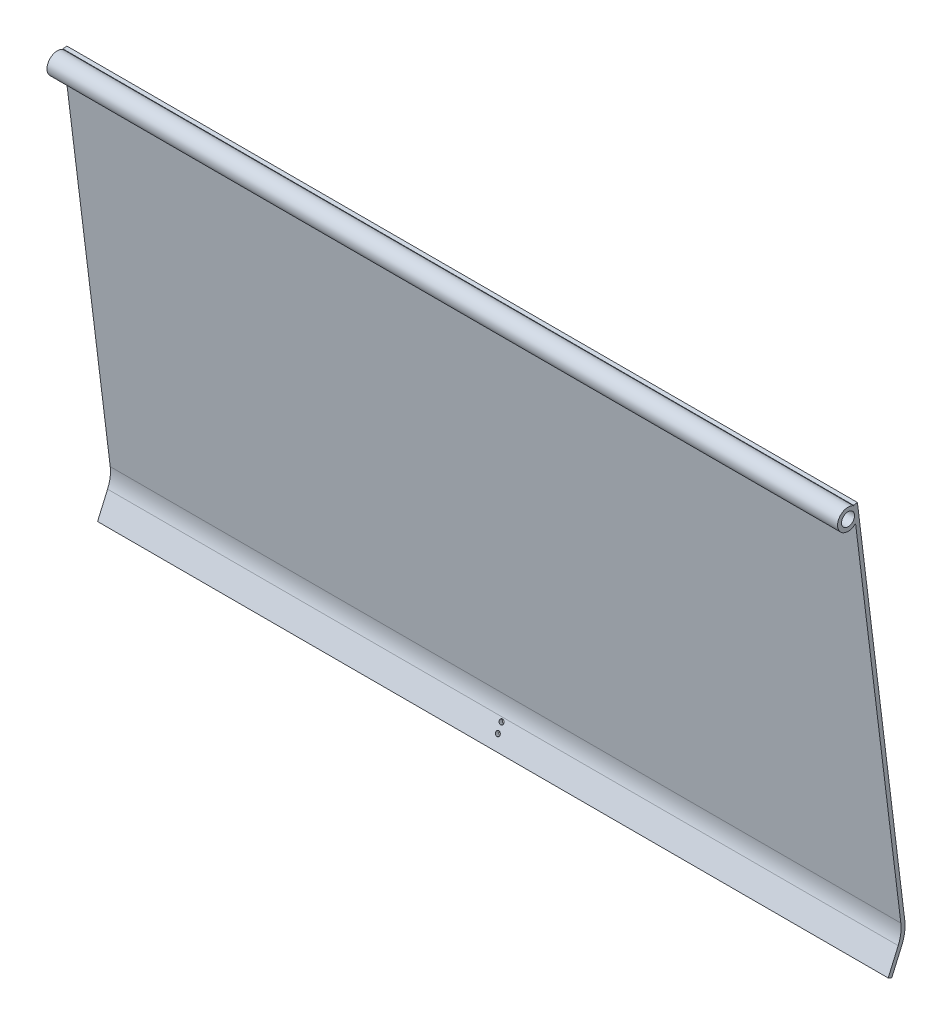
SolidWorks part; units mm, degrees
material "acero"
ref_plane "Alzado" through (0, 0, 0) normal (0, 0, 1) x (1, 0, 0)
ref_plane "Planta" through (0, 0, 0) normal (0, 1, 0) x (1, 0, 0)
ref_plane "Vista lateral" through (0, 0, 0) normal (1, 0, 0) x (0, 0, -1)
sketch "Sketch2" plane through (0, 0, 0) normal (1, 0, 0) x (0, 0, -1)
  line L2 (-441.1427, 5.3017) -> (-407.5476, 82.4956) construction
  line L3 (-405.2791, 98.1232) -> (-441.1997, 390.6725) construction
  line L4 (-441.485, 5.7681) -> (-408.0061, 82.6952)
  line L5 (-405.7754, 98.0623) -> (-441.6959, 390.6116)
  line L7 (-413.8036, 68.1207) -> (-411.0529, 66.9236) construction
  line L8 (-448.8036, 68.1207) -> (-448.8036, 383.1207) construction
  line L9 (-448.8036, 68.1207) -> (-413.8036, 68.1207) construction
  line L10 (-444.2358, 6.9653) -> (-410.7569, 83.8923)
  line L11 (-408.753, 97.6967) -> (-444.6736, 390.246)
  line L12 (-418.3654, 66.4097) -> (-415.6146, 65.2125)
  line L13 (-441.6959, 390.6116) -> (-444.6736, 390.246)
  line L14 (-405.2791, 98.1232) -> (-441.1997, 390.6725) construction
  line L15 (-441.1997, 390.6725) -> (-438.222, 391.0381) construction
  line L16 (-441.1997, 390.6725) -> (-405.2791, 98.1232) construction
  line L17 (-441.0265, 5.5686) -> (-407.5476, 82.4956) construction
  arc A1 (-407.5476, 82.4956) -> (-405.2791, 98.1232) centre (-435.0555, 94.4671) ccw construction
  arc A2 (-408.0061, 82.6952) -> (-405.7754, 98.0623) centre (-435.0555, 94.4671) ccw
  arc A3 (-410.7569, 83.8923) -> (-408.753, 97.6967) centre (-435.0555, 94.4671) ccw
  circle A4 centre (-448.8036, 383.1207) radius 4.9676
  circle A5 centre (-448.8036, 383.1207) radius 7.9676
  dimension "D2" = 315
  dimension "D3" = 35
  dimension "D4" = 3
  dimension "D1" = 0.5
extrude "Main" add sketch "Sketch2" along normal mid plane 600 contours A5 L5 L13 L11 | A5 L11 A3 L10 L12 L4 A2 L5 | A5 L11 | L11 A5 A4 region at (0, 221.9373, 423.0804) region at (0, 388.9276, 442.4547) region at (0, 383.875, 442.6604) region at (0, 386.7921, 444.4609)
ref_axis "Axis1" through (300, 383.1207, 448.8036) along (-1, 0, 0)
sketch "Sketch3" plane through (0, 163.6554, 376.0438) normal (0, 0.3991, 0.9169) x (1, 0, 0)
  line L0 (0, -86.9894) -> (0, -106.0559) construction
  line L1 (-198.9559, -102.6666) -> (198.9559, -102.6666) construction
  line L2 (-198.9559, -102.6666) -> (198.9559, -102.6666)
  line L4 (-300, -86.9894) -> (-300, -106.0559)
  line L5 (-300, -106.0559) -> (300, -106.0559)
  line L6 (300, -106.0559) -> (300, -86.9894)
  line L7 (300, -86.9894) -> (-300, -86.9894)
  line L8 (-300, -86.9894) -> (-300, -106.0559) construction
  line L9 (-300, -106.0559) -> (300, -106.0559) construction
  line L10 (300, -106.0559) -> (300, -86.9894) construction
  line L11 (300, -86.9894) -> (-300, -86.9894) construction
  circle A0 centre (0, -96.5226) radius 1.75
  circle A1 centre (0, -89.6666) radius 1.75
  dimension "D2" = 3.5
  dimension "D3" = 13
  dimension "D1" = 0
extrude "Screw Hole" cut sketch "Sketch3" against normal up to next contours A0 | A1 region at (0, 75.151, 414.5611) region at (0, 81.4375, 411.8252)
